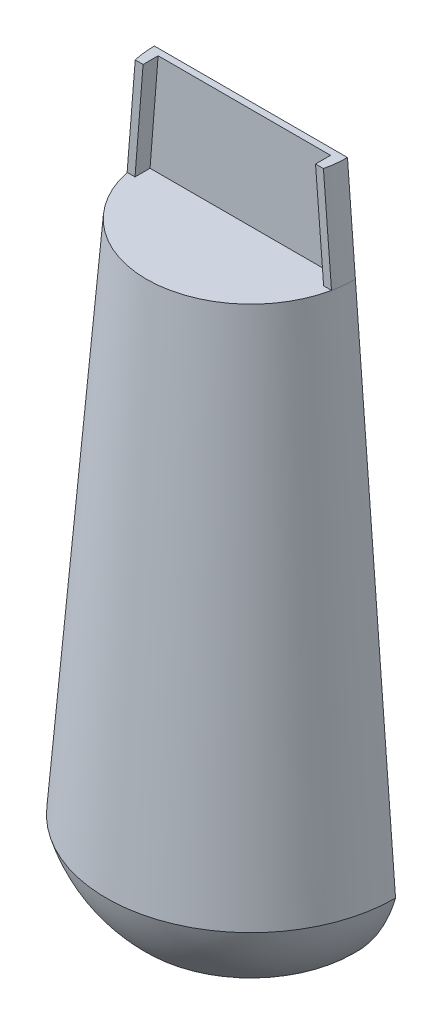
SolidWorks part; units mm, degrees
ref_plane "Front Plane" through (0, 0, 0) normal (0, 0, 1) x (1, 0, 0)
ref_plane "Top Plane" through (0, 0, 0) normal (0, 1, 0) x (1, 0, 0)
ref_plane "Right Plane" through (0, 0, 0) normal (1, 0, 0) x (0, 0, -1)
sketch "Sketch1" plane through (0, 0, 0) normal (0, 0, 1) x (1, 0, 0)
  line L0 (27.686, 0) -> (22.606, 0)
  line L1 (22.606, 0) -> (22.606, 1.8288)
  line L2 (28.829, 4.191) -> (22.606, 4.191)
  line L3 (22.606, 4.191) -> (22.606, 5.8928)
  line L4 (22.606, 5.8928) -> (30.607, 5.8928)
  line L5 (35.8598, 16.2226) -> (0, 16.2226)
  line L6 (0, 16.2226) -> (0, 185.547)
  line L7 (0, 185.547) -> (26.0985, 185.547)
  line L8 (26.0985, 185.547) -> (39.0906, 18.669)
  line L9 (36.5429, 18.669) -> (35.3733, 33.6922) construction
  line L10 (27.686, 0) -> (-9.2457, -34.4394) construction
  line L11 (39.0906, 18.669) -> (56.6975, 77.9254) construction
  line L12 (36.7195, 19.0327) -> (35.0001, 13.4124) construction
  line L13 (32.6347, 8.1905) -> (28.5793, 3.5951) construction
  line L14 (30.8955, 5.835) -> (26.7625, 2.547) construction
  line L15 (22.606, 1.8288) -> (0, 1.8288) construction
  spline S0 degree 3 poles (27.686, 0) (33.0499, 5.0019) (36.8721, 11.2026) (39.0906, 18.669) knots 0 0 0 0 1 1 1 1
  spline S1 degree 3 poles (22.606, 1.8288) (25.0412, 1.8288) (27.1069, 2.821) (28.829, 4.191) knots 0 0 0 0 0.286843 0.286843 0.286843 0.286843
  spline S2 degree 3 poles (30.607, 5.8928) (33.1416, 8.7649) (34.7852, 12.7099) (35.8598, 16.2226) knots 0.392904 0.392904 0.392904 0.392904 0.881974 0.881974 0.881974 0.881974
  dimension "D1" = 185.547
  dimension "D2" = 39.0906
  dimension "D3" = 22.606
  dimension "D4" = 5.08
  dimension "D5" = 1.8288
  dimension "D6" = 2.3622
  dimension "D7" = 6.223
  dimension "D8" = 8.001
  dimension "D9" = 1.7018
  dimension "D10" = 26.0985
  dimension "D11" = 18.669
  dimension "D12" = 2.54
  dimension "D13" = 2.54
  dimension "D14" = 43
  dimension "D15" = 21
revolve "Revolve1" add sketch "Sketch1" angle 180 about L6 reverse direction yes
sketch "Sketch2" plane through (0, 185.547, 0) normal (0, 1, 0) x (1, 0, 0)
  line L0 (-23.3045, -1.778) -> (23.3045, -1.778)
  line L1 (23.3045, -1.778) -> (23.3045, -5.842)
  line L2 (23.3045, -5.842) -> (25.4362, -5.842)
  line L3 (25.4362, -5.842) -> (28.0363, -5.842)
  line L4 (-23.3045, -1.778) -> (-23.3045, -5.842)
  line L5 (-23.3045, -5.842) -> (-25.4362, -5.842)
  line L6 (-25.4362, -5.842) -> (-28.0363, -5.842)
  arc A1 (-26.0985, 0) -> (26.0985, 0) centre (0, 0) ccw construction
  arc A2 (-28.6385, 0) -> (28.6385, 0) centre (0, 0) ccw
  arc A3 (-28.0363, -5.842) -> (28.0363, -5.842) centre (0, 0) ccw
  point P6 (0, -1.778)
  dimension "D1" = 2.54
  dimension "D2" = 46.609
  dimension "D3" = 4.064
  dimension "D4" = 5.842
  dimension "D5" = 2.1317
sketch "Sketch3" plane through (0, 0, 0) normal (0, 0, 1) x (1, 0, 0)
  line L0 (-39.0906, 158.115) -> (39.0906, 158.115)
  dimension "D1" = 158.115
split line "Split Line1"
ref_plane "Plane1" through (0, 158.115, 0) normal (0, 1, 0) x (1, 0, 0)
sketch "Sketch4" plane through (0, 158.115, 0) normal (0, 1, 0) x (1, 0, 0)
  line L0 (-25.4914, -1.778) -> (25.4914, -1.778)
  line L1 (25.4914, -1.778) -> (25.4914, -5.842)
  line L2 (25.4914, -5.842) -> (27.6232, -5.842)
  line L3 (27.6232, -5.842) -> (30.2146, -5.842)
  line L4 (-25.4914, -1.778) -> (-25.4914, -5.842)
  line L5 (-25.4914, -5.842) -> (-27.6232, -5.842)
  line L6 (-27.6232, -5.842) -> (-30.2146, -5.842)
  arc A1 (-28.2342, 0) -> (28.2342, 0) centre (0, 0) ccw construction
  arc A2 (-30.7742, 0) -> (30.7742, 0) centre (0, 0) ccw
  arc A3 (-30.2146, -5.842) -> (30.2146, -5.842) centre (0, 0) ccw
  point P6 (0, -1.778)
  dimension "D2" = 4.064
  dimension "D3" = 5.842
  dimension "D4" = 2.1317
  dimension "D1" = 2.54
loft "Cut-Loft1" cut profiles "Sketch2", "Sketch4" connector at (28.0363, 185.547, 5.842) connector at (30.2146, 158.115, 5.842)
equation "\"D2@Sketch4\"= \"D3@Sketch2\""
equation "\"D3@Sketch4\"= \"D4@Sketch2\""
equation "\"D4@Sketch4\"= \"D5@Sketch2\""
